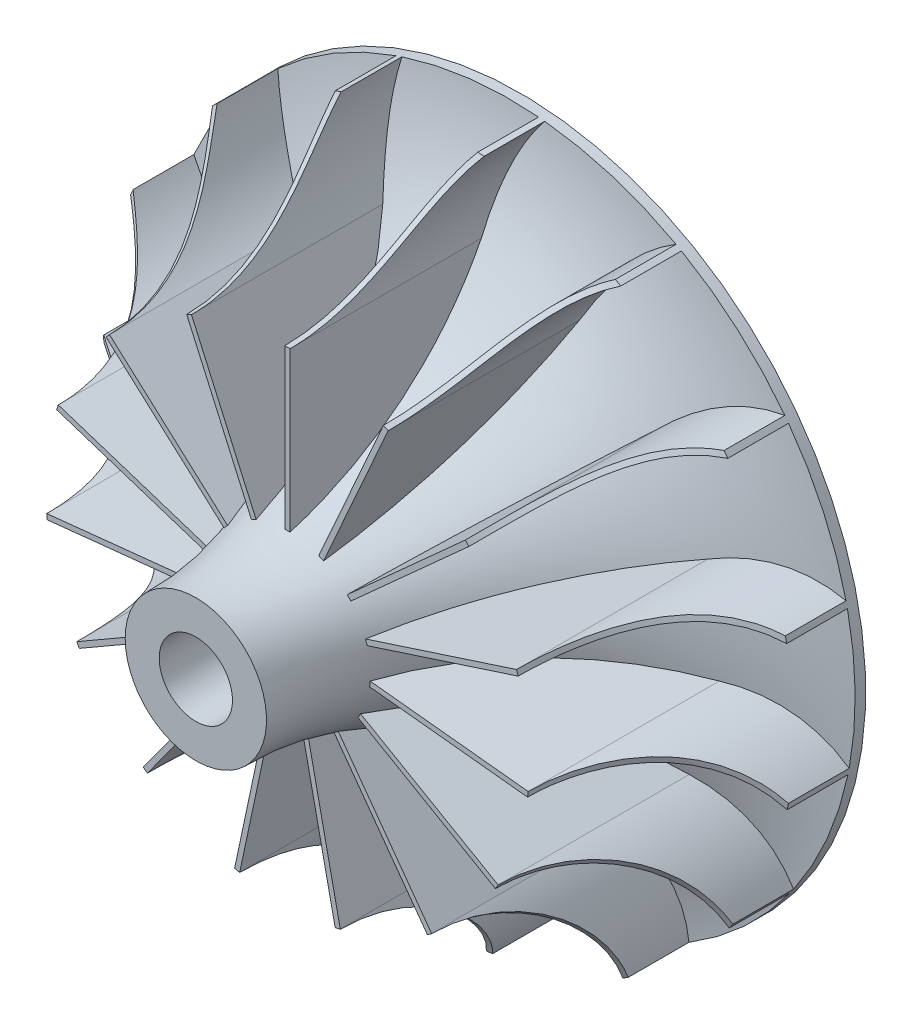
SolidWorks part; units mm, degrees
material "Ti-10V-2Fe-3Al Solution Treated Bar (SS)"
ref_plane "Front Plane" through (0, 0, 0) normal (0, 0, 1) x (1, 0, 0)
ref_plane "Top Plane" through (0, 0, 0) normal (0, 1, 0) x (1, 0, 0)
ref_plane "Right Plane" through (0, 0, 0) normal (1, 0, 0) x (0, 0, -1)
sketch "Sketch1" plane through (0, 0, 0) normal (0, 1, 0) x (1, 0, 0)
  line L0 (0, 31) -> (-33, 31)
  line L1 (-33, 31) -> (-33, 30)
  line L2 (0, 0) -> (-6.75, 0)
  line L3 (0, 31) -> (0, 0) construction
  line L4 (0, 31) -> (0, 0)
  arc A0 (-33, 30) -> (-6.75, 0) centre (-36.4801, 0.4705) cw
  point P0 (0, 31)
revolve "Revolve1" add sketch "Sketch1" angle 360 about L3
sketch "Sketch2" plane through (0, 0, 0) normal (0, 1, 0) x (1, 0, 0)
  line L0 (0.25, 8.75) -> (-0.25, 8.75)
  line L2 (-0.25, 8.75) -> (-0.25, 30)
  line L3 (-0.25, 30) -> (0.25, 30)
  line L4 (-33, 30) -> (33, 30) construction
  line L5 (0.25, 8.75) -> (0.25, 30)
  point P0 (0, 8.75)
  point P11 (0, 30)
  point P12 (0, 8.75)
sketch "Sketch3" plane through (0, 0, 0) normal (0, 0, 1) x (1, 0, 0)
  line L0 (0, 0) -> (0, 23.1)
  arc A0 (0, 23.1) -> (11.4248, 38.178) centre (14.5944, 23.909) cw
sweep "Sweep1" add profiles "Sketch2" path "Sketch3"
sketch "Sketch4" plane through (0, 0, 0) normal (0, 1, 0) x (1, 0, 0)
  circle A0 centre (40.1, 8.75) radius 17
  point P0 (40.1, 8.75)
sketch "Sketch5" plane through (0, 0, 0) normal (0, 0, 1) x (1, 0, 0)
  circle A0 centre (0, 0) radius 40.1
sketch "Sketch6" plane through (0, 0, 0) normal (0, 0, 1) x (1, 0, 0)
  circle A0 centre (0, 0) radius 3.5
pattern_circular "CirPattern5" count 15 over 360 about axis through (0, 0, -30) along (0, 0, -1) of "Sweep1"
sweep "Cut-Sweep1" cut profiles "Sketch4" path "Sketch5"
extrude "Cut-Extrude6" cut sketch "Sketch6" against normal blind 50
sketch "Sketch14" plane through (0, 0, 0) normal (0, 0, 1) x (1, 0, 0)
  circle A0 centre (0, 0) radius 45.3404
  circle A1 centre (0, 0) radius 33
extrude "Cut-Extrude7" cut sketch "Sketch14" against normal blind 50
